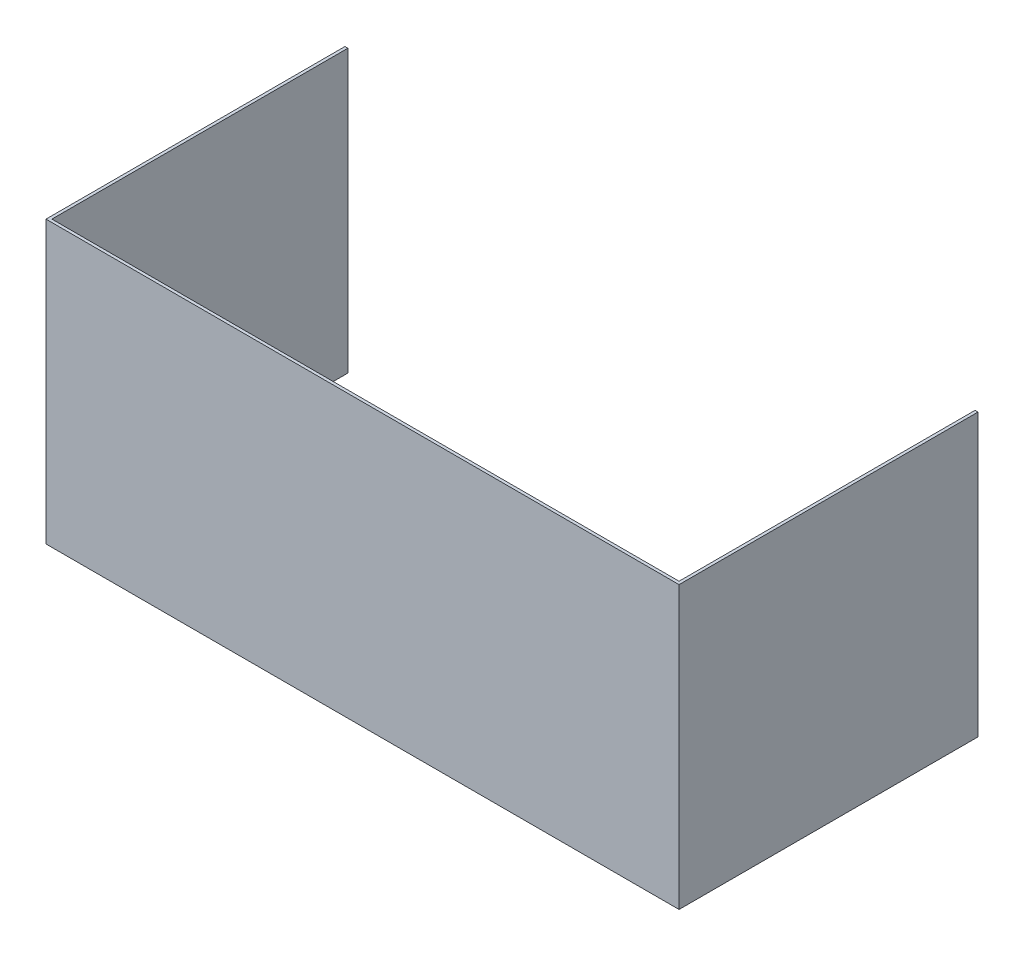
SolidWorks part; units mm, degrees
ref_plane "Front Plane" through (0, 0, 0) normal (0, 0, 1) x (1, 0, 0)
ref_plane "Top Plane" through (0, 0, 0) normal (0, 1, 0) x (1, 0, 0)
ref_plane "Right Plane" through (0, 0, 0) normal (1, 0, 0) x (0, 0, -1)
sketch "Sketch1" plane through (0, 0, 0) normal (0, 1, 0) x (1, 0, 0)
  line L0 (-342.9, -127) -> (-95.25, -127)
  line L1 (-25.4, -196.85) -> (215.9, -196.85) construction
  line L2 (-342.9, -127) -> (-342.9, 196.85)
  line L4 (342.9, -127) -> (342.9, 196.85)
  line L5 (-342.9, -196.85) -> (342.9, 196.85) construction
  line L6 (-342.9, 196.85) -> (342.9, -196.85) construction
  line L7 (-95.25, -127) -> (-25.4, -196.85) construction
  line L8 (215.9, -196.85) -> (285.75, -127) construction
  line L9 (285.75, -127) -> (342.9, -127)
  line L10 (-342.9, -196.85) -> (-342.9, -127) construction
  line L11 (-342.9, -196.85) -> (-25.4, -196.85) construction
  line L12 (215.9, -196.85) -> (342.9, -196.85) construction
  line L13 (342.9, -196.85) -> (342.9, -127) construction
  line L14 (-95.25, -127) -> (285.75, -127)
  point P0 (0, 0)
  dimension "D1" = 685.8
  dimension "D2" = 393.7
  dimension "D3" = 45
  dimension "D4" = 45
  dimension "D5" = 69.85
  dimension "D6" = 317.5
  dimension "D7" = 127
extrude "Extrude-Thin1" add sketch "Sketch1" along normal blind 304.8 thin thin type one direction wall 3.175
ref_plane "Plane1" [suppressed] through (-24.0849, 304.8, 193.675) normal (-1, 0, 0) x (0, 0, 1)
